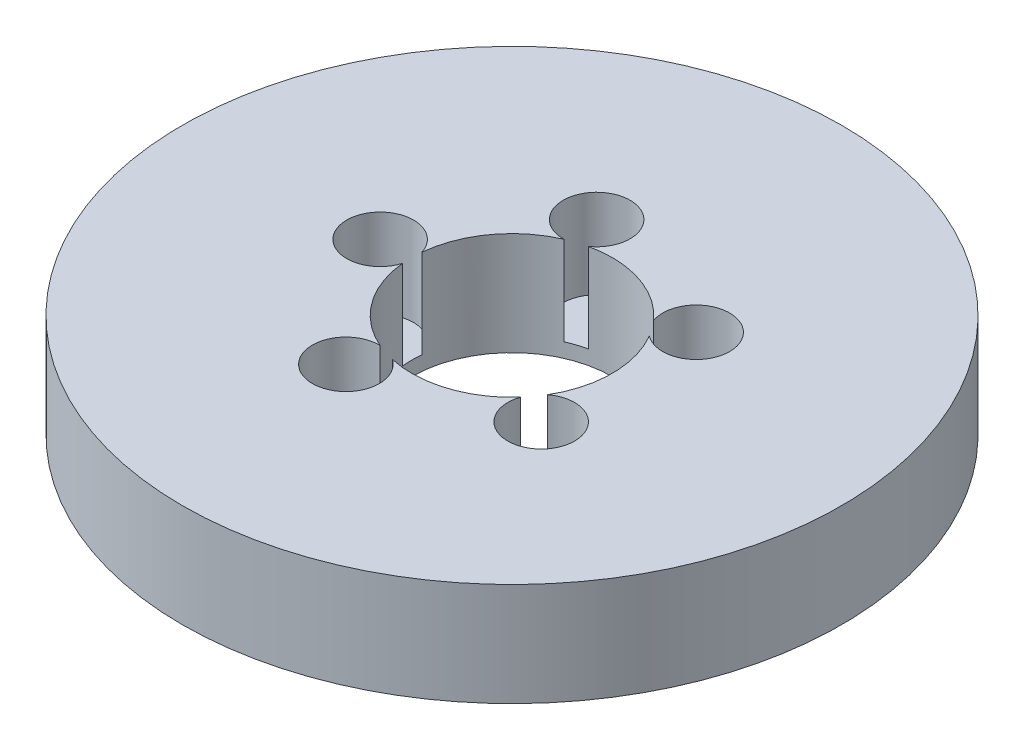
SolidWorks part; units mm, degrees
ref_plane "Front Plane" through (0, 0, 0) normal (0, 0, 1) x (1, 0, 0)
ref_plane "Top Plane" through (0, 0, 0) normal (0, 1, 0) x (1, 0, 0)
ref_plane "Right Plane" through (0, 0, 0) normal (1, 0, 0) x (0, 0, -1)
sketch "Sketch1" plane through (0, 0, 0) normal (0, 1, 0) x (1, 0, 0)
  circle A0 centre (0, 0) radius 57.5
  dimension "FLANGE_OD" = 115
extrude "Boss-Extrude1" add sketch "Sketch1" along normal blind 18
sketch "Sketch2" plane through (0, 0, 0) normal (0, 1, 0) x (1, 0, 0)
  circle A0 centre (0, 0) radius 17.5
  dimension "BORE_D" = 35
extrude "Cut-Extrude1" cut sketch "Sketch2" along normal through all
sketch "Sketch3" plane through (0, 18, 0) normal (0, 1, 0) x (1, 0, 0)
  circle A0 centre (0, 0) radius 23.0034 construction
  circle A1 centre (-23.0034, 0) radius 5.8355
  dimension "BOLT_D" = 11.671
  dimension "BOLT_PCD" = 46.0068
extrude "Cut-Extrude2" cut sketch "Sketch3" against normal blind 15.4938
pattern_circular "CirPattern1" count 5 over 360 about axis through (0, 0, 0) along (0, 1, 0) of "Cut-Extrude2"
